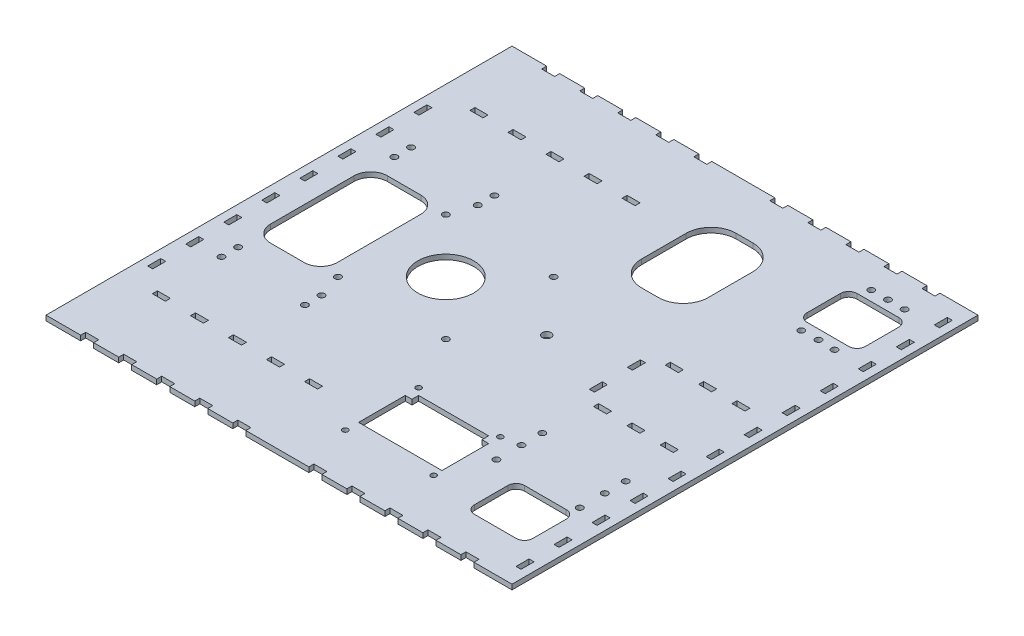
SolidWorks part; units mm, degrees
material "ENPH 253 Hardboard"
ref_plane "Front Plane" through (0, 0, 0) normal (0, 0, 1) x (1, 0, 0)
ref_plane "Top Plane" through (0, 0, 0) normal (0, 1, 0) x (1, 0, 0)
ref_plane "Right Plane" through (0, 0, 0) normal (1, 0, 0) x (0, 0, -1)
sketch "Sketch1" plane through (0, 0, 0) normal (0, 1, 0) x (1, 0, 0)
  line L0 (0, -139.7) -> (0, 139.7) construction
  line L1 (-139.7, 139.7) -> (139.7, 139.7)
  line L2 (-139.7, 139.7) -> (-139.7, -139.7)
  line L3 (-139.7, -139.7) -> (139.7, -139.7)
  line L4 (139.7, 139.7) -> (139.7, -139.7)
  line L5 (-139.7, 139.7) -> (139.7, -139.7) construction
  line L6 (-139.7, -139.7) -> (139.7, 139.7) construction
  line L12 (-139.7, 0) -> (139.7, 0) construction
  point P0 (0, 0)
  dimension "D1" = 279.4
  dimension "D2" = 279.4
extrude "Boss-Extrude1" add sketch "Sketch1" along normal blind 3
sketch "Sketch3" plane through (0, 0, 0) normal (0, -1, 0) x (-1, 0, 0)
  line L0 (-139.7, -139.7) -> (-139.7, 139.7) construction
  line L1 (-134.7, 129.3) -> (-131.7, 129.3)
  line L2 (-134.7, 129.3) -> (-134.7, 121.5)
  line L3 (-134.7, 121.5) -> (-131.7, 121.5)
  line L4 (-131.7, 129.3) -> (-131.7, 121.5)
  line L5 (-139.7, 139.7) -> (139.7, 139.7) construction
  dimension "D1" = 5
  dimension "D2" = 10.4
  dimension "D3" = 7.8
  dimension "D4" = 3
extrude "Cut-Extrude2" cut sketch "Sketch3" against normal through all
pattern_linear "LPattern1" count 12 spacing 22.8 along (0, 0, 1) of "Cut-Extrude2"
sketch "Sketch5" plane through (0, 0, 0) normal (0, -1, 0) x (1, 0, 0)
  line L0 (139.7, -139.7) -> (-139.7, -139.7) construction
  line L1 (109.1, -139.7) -> (116.9, -139.7)
  line L2 (109.1, -139.7) -> (109.1, -136.7)
  line L3 (109.1, -136.7) -> (116.9, -136.7)
  line L4 (116.9, -139.7) -> (116.9, -136.7)
  line L5 (139.7, 139.7) -> (139.7, -139.7) construction
  dimension "D1" = 22.8
  dimension "D2" = 7.8
  dimension "D3" = 3
extrude "Cut-Extrude3" cut sketch "Sketch5" against normal through all
pattern_linear "LPattern2" count 11 spacing 22.8 along (-1, 0, 0) skipping (5, 0) of "Cut-Extrude3"
mirror "Mirror2" about plane through (0, 0, 0) normal (0, 0, 1) of "LPattern2"
sketch "Sketch6" plane through (0, 0, 0) normal (0, -1, 0) x (1, 0, 0)
  line L0 (63.5, -139.7) -> (48.5, -139.7) construction
  line L1 (-134.7, -83.7) -> (-131.7, -83.7)
  line L2 (-134.7, -83.7) -> (-134.7, -75.9)
  line L3 (-134.7, -75.9) -> (-131.7, -75.9)
  line L4 (-131.7, -83.7) -> (-131.7, -75.9)
  line L5 (-139.7, -139.7) -> (-139.7, 139.7) construction
  dimension "D1" = 56
  dimension "D2" = 5
  dimension "D3" = 3
  dimension "D4" = 7.8
extrude "Cut-Extrude4" cut sketch "Sketch6" against normal through all
pattern_linear "LPattern3" count 8 spacing 22.8 along (0, 0, 1) of "Cut-Extrude4"
sketch "Sketch7" plane through (0, 0, 0) normal (0, -1, 0) x (-1, 0, 0)
  line L1 (139.7, 139.7) -> (139.7, -139.7) construction
  line L3 (-63.5, 139.7) -> (-48.5, 139.7) construction
  circle A0 centre (39.7, 0) radius 16.75
  dimension "D1" = 33.5
  dimension "D2" = 100
  dimension "D3" = 139.7
extrude "Cut-Extrude5" cut sketch "Sketch7" against normal through all
hole_wizard "#6 Clearance Hole1" positions "Sketch8" profile "Sketch9" hole size "#6" standard "ANSI Inch" end condition through all
sketch "Sketch8" plane through (0, 3, 0) normal (0, 1, 0) x (1, 0, 0)
  line L0 (-72.025, -32.325) -> (-72.025, 32.325) construction
  line L1 (-72.025, 32.325) -> (-7.375, 32.325) construction
  line L2 (-7.375, 32.325) -> (-7.375, -32.325) construction
  line L3 (-7.375, -32.325) -> (-72.025, -32.325) construction
  point P0 (-72.025, -32.325)
  point P2 (-72.025, 32.325)
  point P4 (-7.375, 32.325)
  point P6 (-7.375, -32.325)
  dimension "D1" = 64.65
  dimension "D2" = 64.65
  dimension "D3" = 90
  dimension "D4" = 64.65
  dimension "D5" = 32.325
  dimension "D6" = 32.325
sketch "Sketch9" plane through (-72.025, 3, 32.325) normal (1, 0, 0) x (0, 0, 1)
  line L0 (0, 0) -> (0, 3)
  line L1 (0, 3) -> (1.8986, 3)
  line L2 (1.8986, 3) -> (1.8986, 0)
  line L5 (1.8986, 0) -> (0, 0)
  line L11 (0, -6.35) -> (0, 107.95) construction
  dimension "Thru Hole Dia." = 3.7973
  dimension "Thru Hole Depth" = 3
hole_wizard "#6 Clearance Hole2" positions "Sketch10" profile "Sketch11" hole size "#6" standard "ANSI Inch" end condition through all
sketch "Sketch10" plane through (0, 3, 0) normal (0, 1, 0) x (1, 0, 0)
  line L1 (-118.9, 139.7) -> (-139.7, 139.7) construction
  line L2 (-139.7, -139.7) -> (-118.9, -139.7) construction
  line L3 (-73.3, 139.7) -> (-88.3, 139.7) construction
  line L4 (-88.3, -139.7) -> (-73.3, -139.7) construction
  line L5 (-139.7, 139.7) -> (-139.7, -139.7) construction
  point P0 (-117.36, 56.83)
  point P2 (-67.36, 56.83)
  point P4 (-117.36, -56.83)
  point P6 (-67.36, -56.83)
  point P22 (-67.36, -46.83)
  point P24 (-117.36, -46.83)
  point P26 (-67.36, 46.83)
  point P28 (-117.36, 46.83)
  dimension "D2" = 50
  dimension "D3" = 22.34
  dimension "D4" = 50
  dimension "D5" = 82.87
  dimension "D6" = 82.87
  dimension "D7" = 82.87
  dimension "D8" = 82.87
  dimension "D9" = 10
  dimension "D10" = 10
  dimension "D11" = 50
  dimension "D12" = 10
  dimension "D13" = 10
  dimension "D14" = 50
  dimension "D15" = 22.34
  dimension "D16" = 22.34
  dimension "D17" = 22.34
sketch "Sketch11" plane through (-117.36, 3, -56.83) normal (1, 0, 0) x (0, 0, 1)
  line L0 (0, 0) -> (0, 3)
  line L1 (0, 3) -> (1.8986, 3)
  line L2 (1.8986, 3) -> (1.8986, 0)
  line L5 (1.8986, 0) -> (0, 0)
  line L11 (0, -6.35) -> (0, 107.95) construction
  dimension "Thru Hole Dia." = 3.7973
  dimension "Thru Hole Depth" = 3
sketch "Sketch14" plane through (0, 0, 0) normal (0, -1, 0) x (-1, 0, 0)
  line L0 (139.7, 139.7) -> (139.7, -139.7) construction
  line L1 (-17.9, 139.7) -> (19.9, 139.7) construction
  circle A0 centre (-20.8, 0) radius 2.65
  dimension "D1" = 5.3
  dimension "D2" = 160.5
  dimension "D3" = 139.7
extrude "Cut-Extrude6" cut sketch "Sketch14" against normal through all
sketch "Sketch16" plane through (0, 0, 0) normal (0, -1, 0) x (1, 0, 0)
  line L0 (-139.7, -139.7) -> (-139.7, 139.7) construction
  line L1 (-118.9, 96.7) -> (-111.1, 96.7)
  line L2 (-118.9, 96.7) -> (-118.9, 93.7)
  line L3 (-118.9, 93.7) -> (-111.1, 93.7)
  line L4 (-111.1, 96.7) -> (-111.1, 93.7)
  line L7 (-111.1, 136.7) -> (-118.9, 136.7) construction
  dimension "D1" = 20.8
  dimension "D2" = 7.8
  dimension "D3" = 40
  dimension "D4" = 3
extrude "Cut-Extrude8" cut sketch "Sketch16" against normal through all
pattern_linear "LPattern5" count 5 spacing 22.8 along (1, 0, 0) of "Cut-Extrude8"
mirror "Mirror4" about plane through (0, 0, 0) normal (0, 0, 1) of "LPattern5"
sketch "Sketch17" plane through (0, 0, 0) normal (0, -1, 0) x (1, 0, 0)
  line L1 (119.7, 23) -> (111.9, 23)
  line L2 (119.7, 23) -> (119.7, 20)
  line L3 (119.7, 20) -> (111.9, 20)
  line L4 (111.9, 23) -> (111.9, 20)
  line L5 (94.1, 139.7) -> (109.1, 139.7) construction
  line L6 (139.7, 139.7) -> (139.7, -139.7) construction
  point P8 (119.7, 21.5)
  dimension "D1" = 116.7
  dimension "D2" = 20
  dimension "D3" = 7.8
  dimension "D4" = 3
extrude "Cut-Extrude9" cut sketch "Sketch17" against normal through all
pattern_linear "LPattern6" count 3 spacing 20 along (-1, 0, 0) of "Cut-Extrude9"
sketch "Sketch18" plane through (0, 0, 0) normal (0, -1, 0) x (-1, 0, 0)
  line L0 (-139.7, -139.7) -> (-139.7, 139.7) construction
  line L1 (-64.7, -15.3) -> (-61.7, -15.3)
  line L2 (-64.7, -15.3) -> (-64.7, -7.5)
  line L3 (-64.7, -7.5) -> (-61.7, -7.5)
  line L4 (-61.7, -15.3) -> (-61.7, -7.5)
  line L5 (-71.3, -139.7) -> (-86.3, -139.7) construction
  dimension "D1" = 7.8
  dimension "D2" = 3
  dimension "D3" = 75
  dimension "D4" = 124.4
extrude "Cut-Extrude10" cut sketch "Sketch18" against normal through all
mirror "Mirror5" about plane through (0, 0, 0) normal (0, 0, 1) of "Cut-Extrude10", "LPattern6", "Cut-Extrude9"
sketch "Sketch19" plane through (0, 0, 0) normal (0, -1, 0) x (1, 0, 0)
  line L0 (0, 0) -> (139.7, 0) construction
  line L1 (24.7, -109.7) -> (34.7, -109.7)
  line L2 (9.7, -94.7) -> (9.7, -68)
  line L3 (24.7, -53) -> (34.7, -53)
  line L4 (49.7, -94.7) -> (49.7, -68)
  line L9 (139.7, 139.7) -> (139.7, -139.7) construction
  line L10 (86.3, -139.7) -> (71.3, -139.7) construction
  line L11 (79.7, -23) -> (71.9, -23) construction
  line L16 (-139.7, -139.7) -> (-139.7, 139.7) construction
  line L17 (-89.7, 35) -> (-109.7, 35)
  line L18 (-79.7, 25) -> (-79.7, -25)
  line L19 (-89.7, -35) -> (-109.7, -35)
  line L20 (-119.7, 25) -> (-119.7, -25)
  line L21 (9.7, 101.7) -> (59.7, 101.7)
  line L22 (9.7, 65.7) -> (59.7, 65.7) construction
  line L23 (9.7, 65.7) -> (9.7, 109.7) construction
  line L24 (9.7, 109.7) -> (59.7, 109.7) construction
  line L25 (59.7, 65.7) -> (59.7, 109.7) construction
  line L29 (13.7, 69.7) -> (55.7, 69.7)
  line L30 (25.7, 139.7) -> (40.7, 139.7) construction
  line L32 (59.7, 101.7) -> (59.7, 73.7) construction
  line L34 (9.7, 101.7) -> (9.7, 73.7) construction
  line L35 (139.7, 139.7) -> (139.7, -139.7) construction
  line L38 (9.7, 101.7) -> (9.7, 73.7)
  line L39 (9.7, 73.7) -> (13.7, 73.7)
  line L40 (13.7, 73.7) -> (13.7, 69.7)
  line L41 (55.7, 69.7) -> (55.7, 73.7)
  line L42 (55.7, 73.7) -> (59.7, 73.7)
  line L43 (59.7, 73.7) -> (59.7, 101.7)
  line L48 (13.7, 69.7) -> (13.7, 105.7) construction
  line L49 (13.7, 105.7) -> (55.7, 105.7) construction
  line L50 (55.7, 69.7) -> (55.7, 105.7) construction
  arc A1 (34.7, -53) -> (49.7, -68) centre (34.7, -68) cw
  arc A2 (34.7, -109.7) -> (49.7, -94.7) centre (34.7, -94.7) ccw
  arc A3 (24.7, -109.7) -> (9.7, -94.7) centre (24.7, -94.7) cw
  arc A4 (9.7, -68) -> (24.7, -53) centre (24.7, -68) cw
  circle A9 centre (-39.7, 0) radius 16.75 construction
  arc A10 (-79.7, -25) -> (-89.7, -35) centre (-89.7, -25) cw
  arc A11 (-89.7, 35) -> (-79.7, 25) centre (-89.7, 25) cw
  arc A12 (-109.7, 35) -> (-119.7, 25) centre (-109.7, 25) ccw
  arc A13 (-109.7, -35) -> (-119.7, -25) centre (-109.7, -25) cw
  point P43 (-79.7, -35)
  point P46 (-79.7, 35)
  dimension "D9" = 35
  dimension "D10" = 10
  dimension "D11" = 44
  dimension "D12" = 50
  dimension "D1" = 15
  dimension "D2" = 30
  dimension "D3" = 90
  dimension "D4" = 30
  dimension "D5" = 40
  dimension "D6" = 70
  dimension "D7" = 20
  dimension "D8" = 40
  dimension "D17" = 30
  dimension "D18" = 80
  dimension "D14" = 4
extrude "Cut-Extrude11" cut sketch "Sketch19" against normal through all
hole_wizard "#4 Clearance Hole1" positions "Sketch20" profile "Sketch21" hole size "#4" standard "ANSI Inch" end condition through all
sketch "Sketch20" plane through (0, 3, 0) normal (0, 1, 0) x (1, 0, 0)
  line L0 (9.7, -101.7) -> (9.7, -73.7) construction
  line L1 (59.7, -73.7) -> (59.7, -101.7) construction
  point P0 (9.7, -65.7)
  point P2 (59.7, -66.7)
  point P4 (59.7, -106.7)
  point P6 (9.7, -109.7)
  point P7 (0, 0)
  point P10 (0, 0)
  point P13 (0, 0)
  point P15 (0, 0)
  point P16 (0, 0)
  point P17 (0, 0)
  point P18 (0, 0)
  point P19 (0, 0)
  point P22 (0, 0)
  dimension "D1" = 8
  dimension "D2" = 8
  dimension "D3" = 5
  dimension "D4" = 1
sketch "Sketch21" plane through (9.7, 3, 65.7) normal (1, 0, 0) x (0, 0, 1)
  line L0 (0, 0) -> (0, 3)
  line L1 (0, 3) -> (1.6319, 3)
  line L2 (1.6319, 3) -> (1.6319, 0)
  line L5 (1.6319, 0) -> (0, 0)
  line L11 (0, -6.35) -> (0, 107.95) construction
  dimension "Thru Hole Dia." = 3.2639
  dimension "Thru Hole Depth" = 3
sketch "Sketch22" plane through (0, 3, 0) normal (0, 1, 0) x (1, 0, 0)
  line L5 (92.2, -84.7) -> (117.2, -84.7)
  line L6 (87.2, -89.7) -> (87.2, -109.7)
  line L7 (92.2, -114.7) -> (117.2, -114.7)
  line L8 (122.2, -89.7) -> (122.2, -109.7)
  line L9 (139.7, -139.7) -> (139.7, 139.7) construction
  line L10 (94.1, -139.7) -> (109.1, -139.7) construction
  line L11 (139.7, 0) -> (94.1968, 0) construction
  line L12 (92.2, 114.7) -> (117.2, 114.7)
  line L13 (122.2, 89.7) -> (122.2, 109.7)
  line L14 (92.2, 84.7) -> (117.2, 84.7)
  line L15 (87.2, 89.7) -> (87.2, 109.7)
  arc A0 (87.2, -109.7) -> (92.2, -114.7) centre (92.2, -109.7) ccw
  arc A1 (92.2, -84.7) -> (87.2, -89.7) centre (92.2, -89.7) ccw
  arc A2 (117.2, -84.7) -> (122.2, -89.7) centre (117.2, -89.7) cw
  arc A3 (117.2, -114.7) -> (122.2, -109.7) centre (117.2, -109.7) ccw
  arc A4 (92.2, 84.7) -> (87.2, 89.7) centre (92.2, 89.7) cw
  arc A5 (122.2, 89.7) -> (117.2, 84.7) centre (117.2, 89.7) cw
  arc A6 (117.2, 114.7) -> (122.2, 109.7) centre (117.2, 109.7) cw
  arc A7 (92.2, 114.7) -> (87.2, 109.7) centre (92.2, 109.7) ccw
  point P2 (87.2, -114.7)
  point P9 (87.2, -84.7)
  point P23 (122.2, -84.7)
  point P26 (122.2, -114.7)
  point P29 (87.2, 84.7)
  point P32 (122.2, 84.7)
  point P35 (122.2, 114.7)
  point P38 (87.2, 114.7)
  dimension "D1" = 5
  dimension "D5" = 17.5
  dimension "D6" = 35
  dimension "D7" = 25
  dimension "D8" = 30
extrude "Cut-Extrude12" cut sketch "Sketch22" against normal up to next contours L8 L5 L6 L7 | L15 L14 L13 L12 region at (104.7, 3, 99.7) region at (104.7, 3, -99.7)
hole_wizard "#6 Clearance Hole3" positions "Sketch25" profile "Sketch26" hole size "#6" standard "ANSI Inch" end condition through all
sketch "Sketch25" plane through (0, 3, 0) normal (0, 1, 0) x (1, 0, 0)
  line L0 (70.35, -52.2) -> (70.35, -79.7) construction
  line L2 (70.35, -79.7) -> (120.35, -79.7) construction
  line L3 (120.35, -79.7) -> (120.35, -52.2) construction
  line L4 (120.35, -52.2) -> (70.35, -52.2) construction
  line L6 (70.35, -64.7) -> (120.35, -64.7) construction
  line L8 (92.2, -84.7) -> (117.2, -84.7) construction
  line L9 (104.7, 79.0309) -> (104.7, 120.7) construction
  line L10 (104.7, 120.7) -> (94.7, 120.7) construction
  line L11 (94.7, 120.7) -> (94.7, 78.7) construction
  line L12 (94.7, 78.7) -> (114.7, 78.7) construction
  line L13 (114.7, 78.7) -> (114.7, 120.7) construction
  line L14 (114.7, 120.7) -> (94.7, 120.7) construction
  line L16 (92.2, 84.7) -> (117.2, 84.7) construction
  line L17 (92.2, 114.7) -> (117.2, 114.7) construction
  point P0 (94.7, 120.7)
  point P2 (114.7, 120.7)
  point P4 (114.7, 78.7)
  point P6 (94.7, 78.7)
  point P8 (104.7, 79.0309)
  point P10 (104.7, 120.7)
  point P12 (70.35, -52.2)
  point P14 (70.35, -79.7)
  point P16 (70.35, -64.7)
  point P18 (120.35, -64.7)
  point P20 (120.35, -52.2)
  point P22 (120.35, -79.7)
  point P43 (104.7, -84.7)
  point P56 (104.7, 84.7)
  dimension "D1" = 27.5
  dimension "D2" = 5
  dimension "D3" = 15
  dimension "D4" = 50
  dimension "D5" = 15.65
  dimension "D6" = 20
  dimension "D7" = 10
  dimension "D8" = 6
  dimension "D9" = 6
sketch "Sketch26" plane through (94.7, 3, -120.7) normal (1, 0, 0) x (0, 0, 1)
  line L0 (0, 0) -> (0, 3)
  line L1 (0, 3) -> (1.8986, 3)
  line L2 (1.8986, 3) -> (1.8986, 0)
  line L5 (1.8986, 0) -> (0, 0)
  line L11 (0, -6.35) -> (0, 107.95) construction
  dimension "Thru Hole Dia." = 3.7973
  dimension "Thru Hole Depth" = 3
equation "\"45mmm\"=50"
